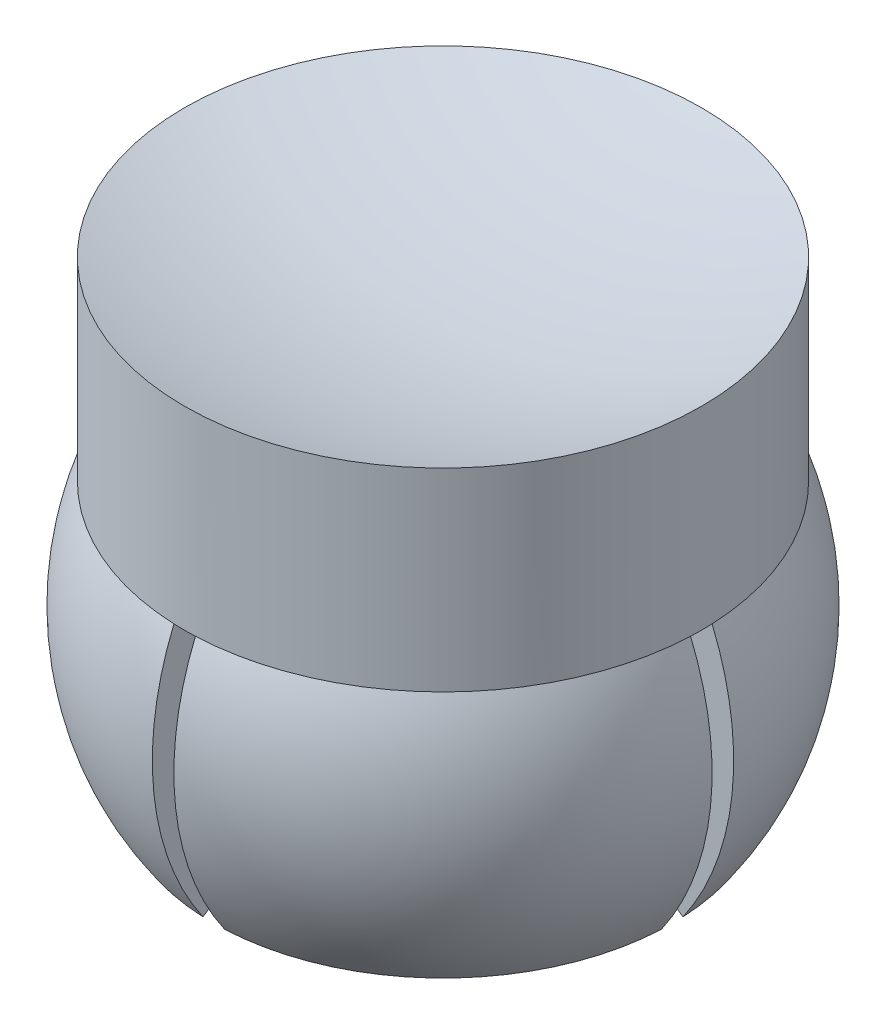
SolidWorks part; units mm, degrees
other "Markup1"
sketch "Sketch3" plane through (-5.9948, -3.4415, 5.9948) normal (0, 0, 1) x (1, 0, 0)
ref_plane "Front Plane" through (0, 0, 0) normal (0, 0, 1) x (1, 0, 0)
ref_plane "Top Plane" through (0, 0, 0) normal (0, 1, 0) x (1, 0, 0)
ref_plane "Right Plane" through (0, 0, 0) normal (1, 0, 0) x (0, 0, -1)
sketch "Sketch1" plane through (0, 0, 0) normal (0, 0, 1) x (1, 0, 0)
  line L1 (0, 6) -> (0, 5)
  line L4 (4.0958, -2.8679) -> (5.3245, -3.7282)
  line L5 (0, 0) -> (3.8805, 0) construction
  line L6 (0, 0) -> (4.0958, -2.8679) construction
  line L11 (0, 6) -> (-2.0586, 6) construction
  line L12 (6, 7) -> (6, 2.5)
  arc A0 (4.0958, -2.8679) -> (0, 5) centre (0, 0) ccw
  arc A1 (5.3245, -3.7282) -> (6, 2.5) centre (0, 0) ccw
  arc A3 (6, 7) -> (0, 6) centre (0, 24.5) cw
  point P3 (5, 5.9871)
  point P6 (0, 7.1843)
  point P9 (3.8805, 8)
  point P13 (5, 8.0492)
  point P15 (0, 0)
  point P16 (5, 7.9293)
  point P17 (5, 5.8672)
  point P18 (0, 0)
  point P19 (5, 8.8361)
  point P20 (4.2779, 4.8939)
  point P21 (0, 6.1248)
  dimension "D1" = 5
  dimension "D2" = 13
  dimension "D6" = 1
  dimension "D5" = 2
  dimension "D3" = 35
  dimension "D4" = 6
revolve "Revolve1" add sketch "Sketch1" angle 360 about L1
sketch "Sketch2" plane through (0, 0, 0) normal (0, 0, 1) x (1, 0, 0)
  line L0 (-0.25, -3.7282) -> (-0.25, 2.5)
  line L1 (-0.25, -3.7282) -> (0.25, -3.7282)
  line L2 (-0.25, 2.5) -> (0.25, 2.5)
  line L3 (0.25, -3.7282) -> (0.25, 2.5)
  line L4 (5.3245, -3.7282) -> (-5.3245, -3.7282) construction
  line L7 (-6, 2.5) -> (6, 2.5) construction
  point P6 (0, 2.5)
  dimension "D1" = 0.5
extrude "Cut-Extrude1" cut sketch "Sketch2" against normal blind 10
pattern_circular "CirPattern1" count 4 over 360 about axis through (0, -3.7282, 0) along (0, 1, 0) of "Cut-Extrude1"
